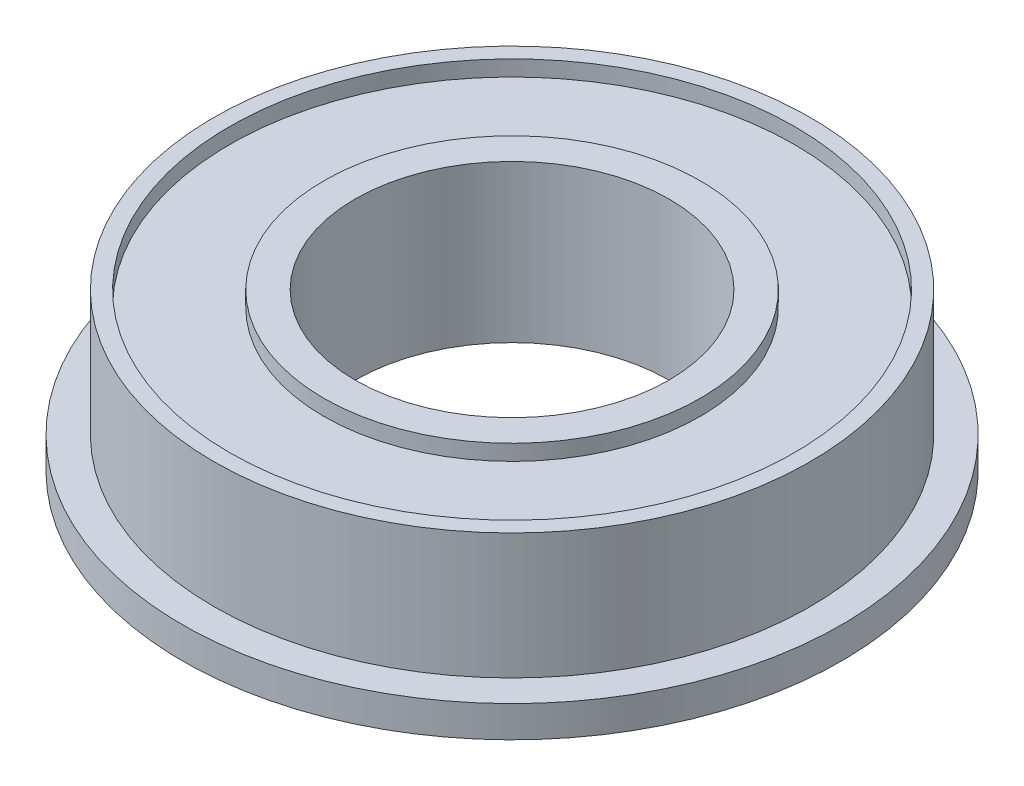
SolidWorks part; units mm, degrees
ref_plane "前视基准面" through (0, 0, 0) normal (0, 0, 1) x (1, 0, 0)
ref_plane "上视基准面" through (0, 0, 0) normal (0, 1, 0) x (1, 0, 0)
ref_plane "右视基准面" through (0, 0, 0) normal (1, 0, 0) x (0, 0, -1)
sketch "草图1" plane through (0, 0, 0) normal (0, 1, 0) x (1, 0, 0)
  circle A0 centre (0, 0) radius 9.5
extrude "凸台-拉伸1" add sketch "草图1" along normal blind 4
sketch "草图2" plane through (0, 0, 0) normal (0, -1, 0) x (1, 0, 0)
  circle A0 centre (0, 0) radius 10.5
extrude "凸台-拉伸2" add sketch "草图2" along normal blind 1
sketch "草图3" plane through (0, 4, 0) normal (0, 1, 0) x (1, 0, 0)
  circle A0 centre (0, 0) radius 5
extrude "切除-拉伸1" cut sketch "草图3" against normal up to next
sketch "草图4" plane through (0, 4, 0) normal (0, 1, 0) x (1, 0, 0)
  circle A0 centre (0, 0) radius 6
  circle A1 centre (0, 0) radius 9
extrude "切除-拉伸2" cut sketch "草图4" against normal blind 0.5
extrude "切除-拉伸5" cut sketch "草图4<2>" along normal blind 0.5 from surface starting at face at (0, -1, -5)
sketch "草图4<2>" plane through (0, 4, 0) normal (0, 1, 0) x (1, 0, 0) same geometry as "草图4"
